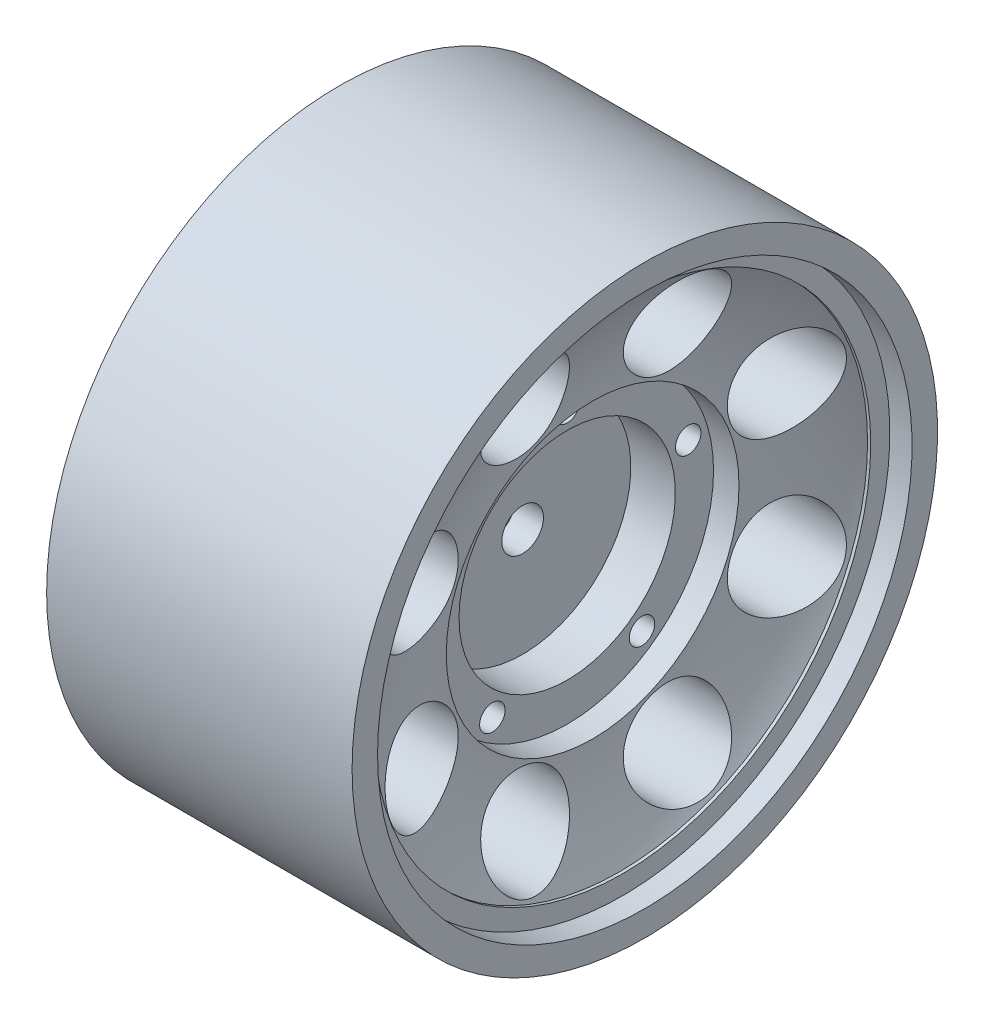
SolidWorks part; units mm, degrees
ref_plane "Front Plane" through (0, 0, 0) normal (0, 0, 1) x (1, 0, 0)
ref_plane "Top Plane" through (0, 0, 0) normal (0, 1, 0) x (1, 0, 0)
ref_plane "Right Plane" through (0, 0, 0) normal (1, 0, 0) x (0, 0, -1)
sketch "Sketch1" plane through (0, 0, 0) normal (0, 1, 0) x (1, 0, 0)
  line L0 (0, 0) -> (4.9, 0) construction
  line L1 (8.4, 1.6383) -> (8.4, 8.5)
  line L2 (8.4, 8.5) -> (11.9, 8.5)
  line L3 (11.9, 8.5) -> (11.9, 11.5)
  line L4 (11.9, 11.5) -> (13.9, 11.5)
  line L5 (16, 19.5) -> (16.25, 19.5)
  line L6 (16.25, 19.5) -> (16.25, 21)
  line L7 (16.25, 21) -> (18, 21)
  line L8 (18, 21) -> (18, 23)
  line L9 (18, 23) -> (-6, 23)
  line L10 (-6, 23) -> (-6, 21.25)
  line L11 (-6, 21.25) -> (-4.25, 19.5)
  line L12 (-4.25, 19.5) -> (7, 19.5)
  line L13 (7, 19.5) -> (7, 8.5)
  line L14 (7, 8.5) -> (0, 8.5)
  line L15 (0, 8.5) -> (0, 1.6383)
  line L16 (13.9, 11.5) -> (13.9, 23) construction
  line L17 (8.4, 1.6383) -> (0, 1.6383)
  arc A0 (13.9, 11.5) -> (16, 19.5) centre (30.1881, 11.5) cw
  point P15 (0, 0)
  point P20 (0, 0)
  point P21 (3.6816, 8.5)
  dimension "D1" = 24
  dimension "D2" = 2
  dimension "D3" = 1.5
  dimension "D4" = 8
  dimension "D5" = 3
  dimension "D6" = 23
  dimension "D7" = 1.75
  dimension "D8" = 1.75
  dimension "D9" = 0.25
  dimension "D10" = 2
  dimension "D11" = 3.5
  dimension "D12" = 1.6383
  dimension "D13" = 45
  dimension "D14" = 7
  dimension "D15" = 11.25
  dimension "D16" = 2.1
revolve "Revolve1" add sketch "Sketch1" angle 360 about L0
sketch "Sketch2" plane through (0, 0, 0) normal (1, 0, 0) x (0, 0, -1)
  circle A0 centre (-5.9316, 14.3201) radius 3.75
  circle A1 centre (5.9316, 14.3201) radius 3.75
  circle A2 centre (14.3201, 5.9316) radius 3.75
  circle A3 centre (14.3201, -5.9316) radius 3.75
  circle A4 centre (5.9316, -14.3201) radius 3.75
  circle A5 centre (-5.9316, -14.3201) radius 3.75
  circle A6 centre (-14.3201, -5.9316) radius 3.75
  circle A7 centre (-14.3201, 5.9316) radius 3.75
  circle A8 centre (0, 0) radius 11.5 construction
  circle A9 centre (0, 0) radius 19.5 construction
  circle A10 centre (0, 0) radius 11.5 construction
  circle A11 centre (0, 0) radius 19.5 construction
  point P2 (5.9866, 14.5084)
  point P3 (-2.1381, -3.2682)
  point P18 (0, 0)
  point P20 (-14.2043, 5.8836)
  point P27 (-5.9161, 14.2826)
  dimension "D2" = 7.5
  dimension "D3" = 15.5
  dimension "D1" = 8
extrude "Cut-Extrude2" cut sketch "Sketch2" against normal through all both and the other way through all
sketch "Sketch3" plane through (11.9, 0, 0) normal (1, 0, 0) x (0, 0, -1)
  circle A0 centre (0, 10) radius 1
  circle A1 centre (9.5106, 3.0902) radius 1
  circle A2 centre (5.8779, -8.0902) radius 1
  circle A3 centre (-5.8779, -8.0902) radius 1
  circle A4 centre (-9.5106, 3.0902) radius 1
  point P2 (-0.2987, 6.463)
  point P3 (0, 0)
  point P12 (0, 0)
  point P13 (-0.9624, -0.6276)
  point P15 (-9.4396, 3.0671)
  dimension "D3" = 2
  dimension "D2" = 10
  dimension "D1" = 5
extrude "Cut-Extrude3" cut sketch "Sketch3" against normal up to next
sketch "Sketch4" plane through (0, 0, 0) normal (-1, 0, 0) x (0, 0, 1)
  line L1 (6.9282, 0) -> (3.4641, 6)
  line L2 (3.4641, 6) -> (-3.4641, 6)
  line L3 (-3.4641, 6) -> (-6.9282, 0)
  line L4 (-6.9282, 0) -> (-3.4641, -6)
  line L5 (-3.4641, -6) -> (3.4641, -6)
  line L6 (3.4641, -6) -> (6.9282, 0)
  circle A0 centre (0, 0) radius 6 construction
  point P1 (0, 0)
  dimension "D1" = 12
extrude "Cut-Extrude4" cut sketch "Sketch4" against normal blind 6.148
